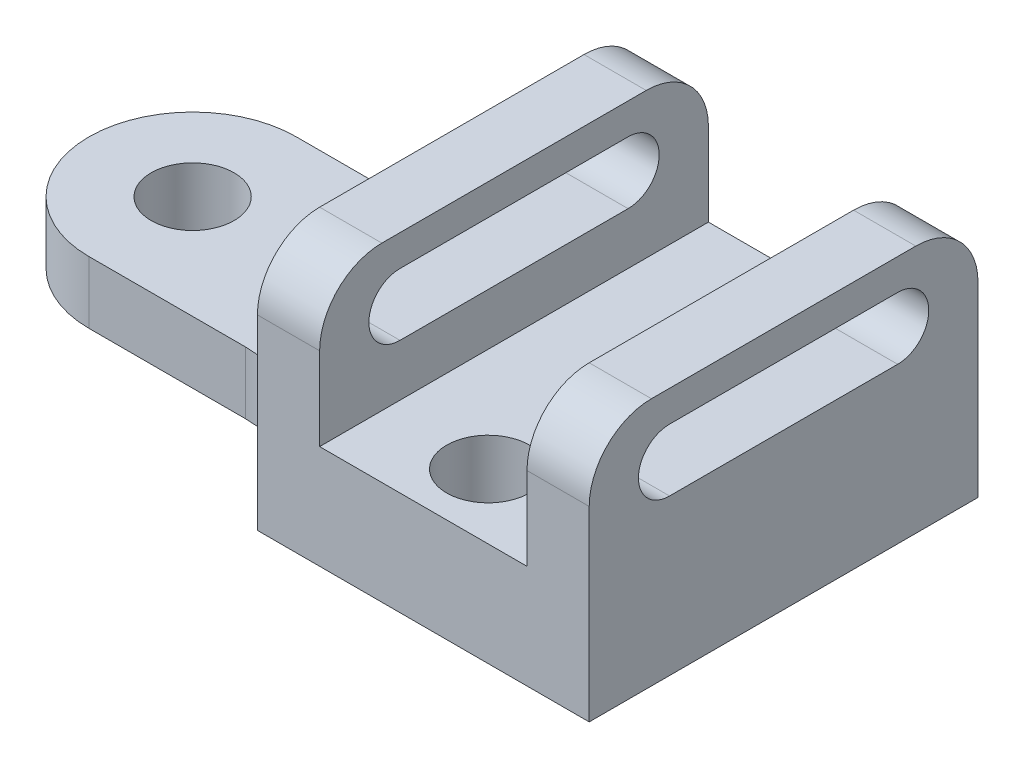
SolidWorks part; units mm, degrees
ref_plane "Front Plane" through (0, 0, 0) normal (0, 0, 1) x (1, 0, 0)
ref_plane "Top Plane" through (0, 0, 0) normal (0, 1, 0) x (1, 0, 0)
ref_plane "Right Plane" through (0, 0, 0) normal (1, 0, 0) x (0, 0, -1)
sketch "Sketch2" plane through (0, 0, 0) normal (0, 0, 1) x (1, 0, 0)
  line L0 (0, 0) -> (64, 0)
  line L1 (64, 0) -> (64, 48)
  line L2 (64, 48) -> (52, 48)
  line L3 (52, 48) -> (52, 20)
  line L4 (52, 20) -> (12, 20)
  line L5 (12, 20) -> (12, 48)
  line L6 (12, 48) -> (0, 48)
  line L7 (0, 48) -> (0, 0)
  line L8 (0, 0) -> (-70, 0)
  line L9 (-70, 0) -> (-70, 12)
  line L10 (-70, 12) -> (0, 12)
  dimension "D1" = 64
  dimension "D2" = 48
  dimension "D3" = 12
  dimension "D4" = 40
  dimension "D5" = 28
  dimension "D6" = 12
  dimension "D7" = 48
  dimension "D8" = 70
  dimension "D9" = 12
extrude "Boss-Extrude2" add sketch "Sketch2" against normal blind 75 contours L6 L7 L0 L1 L2 L3 L4 L5 | L10 L9 L8 L7 region at (32, 18.2623, 0) region at (-35, 6, 0)
sketch "Sketch4" plane through (0, 12, 0) normal (0, 1, 0) x (1, 0, 0)
  line L0 (0, 37.5) -> (-50, 37.5) construction
  line L1 (0, 75) -> (0, 0) construction
  line L2 (-50, 57.5) -> (0, 57.5)
  line L3 (-50, 17.5) -> (0, 17.5)
  line L4 (0, 57.5) -> (0, 75)
  line L5 (0, 75) -> (-70, 75)
  line L6 (-70, 75) -> (-70, 37.5)
  line L7 (-70, 37.5) -> (-70, 0)
  line L8 (-70, 0) -> (0, 0)
  line L9 (0, 0) -> (0, 17.5)
  circle A0 centre (-50, 37.5) radius 8
  circle A1 centre (-50, 37.5) radius 20
  line M3 (-70, 0) -> (0, 0)
  line M4 (0, 0) -> (0, 75)
  line M5 (0, 75) -> (-70, 75)
  line M6 (-70, 75) -> (-70, 0)
  dimension "D2" = 16
  dimension "D3" = 40
  dimension "D1" = 50
extrude "Cut-Extrude2" cut sketch "Sketch4" against normal blind 75 contours A1 L2 M4 M5 M6 | A1 L3 M6 M3 M4 region at (-36.9994, 12, -65.3845) region at (-36.9994, 12, -9.6155)
fillet "Fillet2" radius 20 2 edges at (0, 6, -57.5) (0, 6, -17.5)
sketch "Sketch11" plane through (0, 12, 0) normal (0, 1, 0) x (1, 0, 0)
  circle A0 centre (-50, 37.5) radius 8
  circle A1 centre (31.1281, 62.5) radius 8
  circle A2 centre (31.1281, 12.5) radius 8
  dimension "D1" = 16
  dimension "D3" = 16
  dimension "D4" = 50
extrude "Cut-Extrude9" cut sketch "Sketch11" against normal blind 20 contours A0
sketch "Sketch13" plane through (0, 20, 0) normal (0, 1, 0) x (1, 0, 0)
  line L0 (12, 37.5) -> (52, 37.5) construction
  line L1 (12, 75) -> (12, 0) construction
  line L2 (52, 75) -> (52, 0) construction
  circle A0 centre (32, 62.5) radius 8
  circle A1 centre (32, 12.5) radius 8
  dimension "D2" = 16
  dimension "D3" = 20
  dimension "D1" = 50
extrude "Cut-Extrude10" cut sketch "Sketch13" against normal through all contours A0 | A1
sketch "Sketch14" plane through (64, 0, 0) normal (1, 0, 0) x (0, 0, -1)
  line L0 (15.5, 36) -> (59.5, 36) construction
  line L1 (15.5, 42) -> (59.5, 42)
  line L2 (15.5, 30) -> (59.5, 30)
  line L3 (37.5, 48) -> (37.5, 0) construction
  line L4 (75, 48) -> (0, 48) construction
  line L5 (75, 0) -> (0, 0) construction
  arc A0 (15.5, 42) -> (15.5, 30) centre (15.5, 36) ccw
  arc A1 (59.5, 30) -> (59.5, 42) centre (59.5, 36) ccw
  point P2 (37.5, 36)
  dimension "D2" = 6
  dimension "D1" = 44
  dimension "D3" = 0
  dimension "D4" = 12
extrude "Cut-Extrude11" cut sketch "Sketch14" against normal through all contours L2 A1 L1 A0
fillet "Fillet3" radius 12 4 edges at (6, 48, -75) (58, 48, -75) (58, 48, 0) (6, 48, 0)
